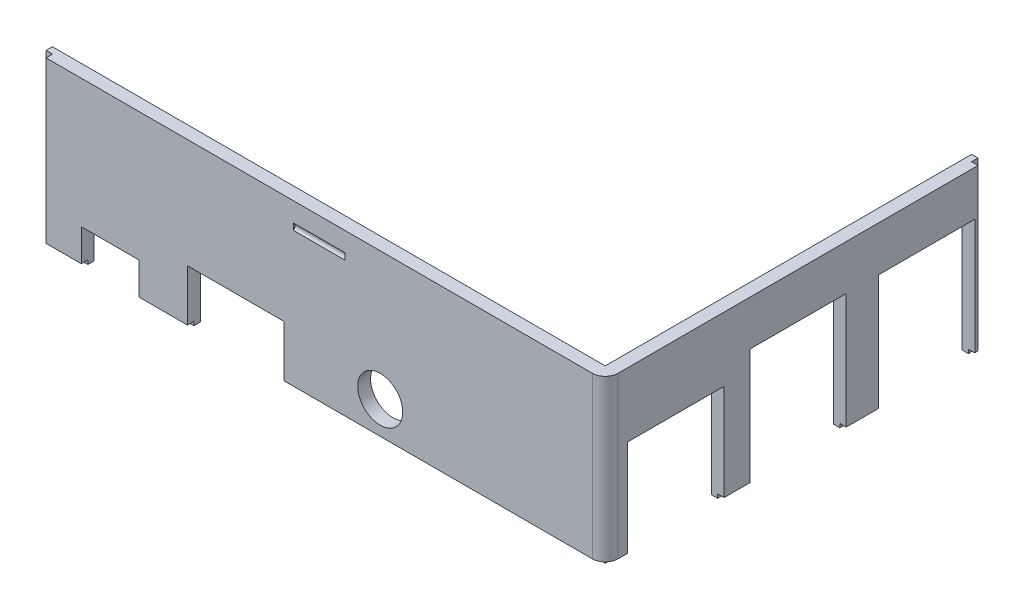
SolidWorks part; units mm, degrees
ref_plane "Přední rovina" through (0, 0, 0) normal (0, 0, 1) x (1, 0, 0)
ref_plane "Horní rovina" through (0, 0, 0) normal (0, 1, 0) x (1, 0, 0)
ref_plane "Pravá rovina" through (0, 0, 0) normal (1, 0, 0) x (0, 0, -1)
sketch "Skica1" plane through (0, 0, 0) normal (0, 1, 0) x (1, 0, 0)
  line L1 (0, 0) -> (88, 0)
  line L2 (0, 0) -> (0, 2)
  line L3 (0, 2) -> (88, 2)
  line L4 (88, 0) -> (88, 2)
  line L9 (88, 2) -> (86, 2)
  line L10 (88, 2) -> (88, 59)
  line L11 (88, 59) -> (86, 59)
  line L12 (86, 2) -> (86, 59)
  line L17 (0, 0) -> (1, 0)
  line L18 (0, 0) -> (0, 1)
  line L19 (0, 1) -> (1, 1)
  line L20 (1, 0) -> (1, 1)
  line L21 (88, 59) -> (87, 59)
  line L22 (88, 59) -> (88, 58)
  line L23 (88, 58) -> (87, 58)
  line L24 (87, 59) -> (87, 58)
  dimension "D1" = 2
  dimension "D2" = 88
  dimension "D3" = 1
  dimension "D4" = 57
  dimension "D5" = 2
  dimension "D6" = 1
extrude "Přidat vysunutím1" add sketch "Skica1" along normal blind 25 contours L24 L11 L12 L3 L10 L23 | L20 L1 L4 L3 L2 L19 region at (44.2486, 0, -1.0029) region at (86.9956, 0, -30.2522)
sketch "Skica2" plane through (0, 0, 0) normal (0, -1, 0) x (1, 0, 0)
  line L0 (0, -1) -> (0, -2) construction
  line L1 (0, -1) -> (86, -1)
  line L2 (0, -1) -> (0, -2)
  line L3 (0, -2) -> (86, -2)
  line L4 (86, -1) -> (86, -2)
  line L5 (87, -59) -> (86, -59)
  line L6 (87, -59) -> (87, -1)
  line L7 (87, -1) -> (86, -1)
  line L8 (86, -59) -> (86, -1)
  line L9 (0, -1) -> (1, -1) construction
extrude "Přidat vysunutím2" add sketch "Skica2" along normal blind 0.6 contours L4 L3 L2 L1 | L8 L5 L6 L7
sketch "Skica5" plane through (0, 0, 0) normal (0, 0, 1) x (1, 0, 0)
  line L1 (6.5, 5) -> (15.5, 5)
  line L2 (6.5, 5) -> (6.5, -0.6)
  line L3 (6.5, -0.6) -> (15.5, -0.6)
  line L4 (15.5, 5) -> (15.5, -0.6)
  line L5 (11, 5) -> (11, -0.7728) construction
  line L6 (0, 25) -> (0, 0) construction
  line L7 (0, -0.6) -> (0, 25) construction
  line L8 (23, -0.6) -> (38, -0.6)
  line L9 (23, -0.6) -> (23, 8)
  line L10 (23, 8) -> (38, 8)
  line L11 (38, -0.6) -> (38, 8)
  line L12 (1, 0) -> (87, 0) construction
  line L13 (0, -0.6) -> (86, -0.6) construction
  line L14 (1, 0) -> (88, 0) construction
  line L15 (0, -0.6) -> (87, -0.6) construction
  circle A0 centre (53, 5) radius 3.5
  dimension "D7" = 7
  dimension "D9" = 5
  dimension "D1" = 5
  dimension "D2" = 9
  dimension "D3" = 11
  dimension "D4" = 23
  dimension "D5" = 15
  dimension "D6" = 8
  dimension "D8" = 53
extrude "Odebrat vysunutím1" cut sketch "Skica5" against normal up to next
sketch "Skica6" plane through (88, 0, 0) normal (1, 0, 0) x (0, 0, -1)
  line L1 (3.5, -0.6) -> (18.5, -0.6)
  line L2 (3.5, -0.6) -> (3.5, 15)
  line L3 (3.5, 15) -> (18.5, 15)
  line L4 (18.5, -0.6) -> (18.5, 15)
  line L9 (42.5, -0.6) -> (57.5, -0.6)
  line L10 (42.5, -0.6) -> (42.5, 18)
  line L11 (42.5, 18) -> (57.5, 18)
  line L12 (57.5, -0.6) -> (57.5, 18)
  line L13 (11, 15) -> (11, -0.6) construction
  line L18 (22.5, -0.6) -> (37.5, -0.6)
  line L19 (22.5, -0.6) -> (22.5, 18)
  line L20 (22.5, 18) -> (37.5, 18)
  line L21 (37.5, -0.6) -> (37.5, 18)
  line L22 (30, 18) -> (30, -0.6) construction
  line L24 (50, 18) -> (50, -0.6) construction
  line L27 (1, -0.6) -> (1, 0) construction
  line L28 (59, -0.6) -> (1, -0.6) construction
  line L29 (0, 0) -> (58, 0) construction
  line L30 (58, 0) -> (1, 0) construction
  line L31 (59, -0.6) -> (59, 25) construction
  point P28 (59, 12.2)
  dimension "D1" = 10
  dimension "D2" = 29
  dimension "D3" = 9
  dimension "D4" = 15
  dimension "D5" = 15
  dimension "D6" = 15
  dimension "D7" = 18
  dimension "D8" = 15
  dimension "D9" = 18
extrude "Odebrat vysunutím2" cut sketch "Skica6" against normal up to next
fillet "Fillet1" radius 2 1 edges at (88, 12.5, 0)
sketch "Sketch1" plane through (88, 0, 0) normal (1, 0, 0) x (0, 0, -1)
  line L0 (0, 21.5) -> (-0.4, 21.5)
  line L1 (0, 0) -> (0, 25) construction
  line L2 (2, 25) -> (58, 25) construction
  line L3 (0, 22) -> (0, 21)
  arc A0 (0, 22) -> (0, 21) centre (-0.4, 21.5) cw
  dimension "D2" = 1
  dimension "D1" = 0.4
  dimension "D3" = 4
extrude "Cut-Extrude1" cut sketch "Sketch1" against normal blind 8 from offset 40.5 contours A0 L3 region at (88, 21.5, -0.0979) offset against normal yes
